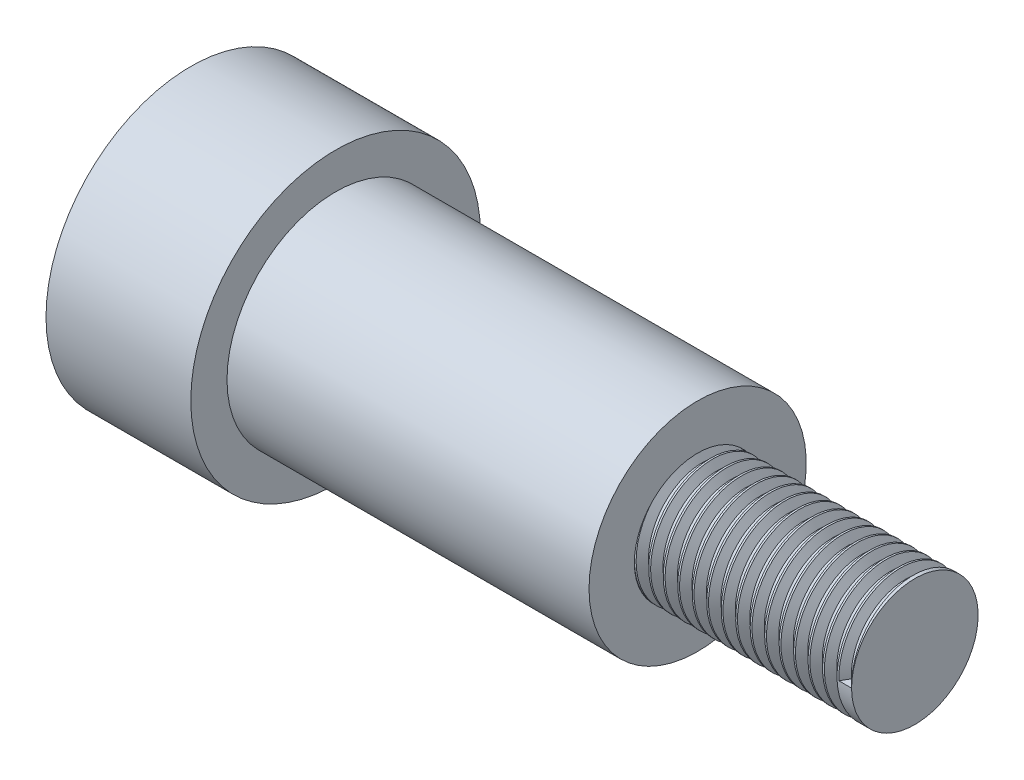
SolidWorks part; units mm, degrees
ref_plane "Front Plane" through (0, 0, 0) normal (0, 0, 1) x (1, 0, 0)
ref_plane "Top Plane" through (0, 0, 0) normal (0, 1, 0) x (1, 0, 0)
ref_plane "Right Plane" through (0, 0, 0) normal (1, 0, 0) x (0, 0, -1)
sketch "Sketch1" plane through (0, 0, 0) normal (0, 0, 1) x (1, 0, 0)
  line L0 (0, 0) -> (63.5, 0)
  line L1 (63.5, 0) -> (63.5, 5.5499)
  line L2 (63.5, 5.5499) -> (44.45, 5.5499)
  line L3 (12.7, 9.525) -> (12.7, 12.7)
  line L4 (12.7, 12.7) -> (0, 12.7)
  line L5 (0, 12.7) -> (0, 0)
  line L6 (12.7, 9.525) -> (44.45, 9.525)
  line L7 (44.45, 9.525) -> (44.45, 5.5499)
  dimension "D1" = 31.75
  dimension "D2" = 5.5499
  dimension "D3" = 12.7
  dimension "D4" = 12.7
  dimension "D5" = 19.05
  dimension "D6" = 9.525
revolve "Revolve1" add sketch "Sketch1" angle 360 about L0
thread "Thread1" pitch 1.27 method cut profile "Thread Profile1" start angle 0, offset 0, length 0, pitch 1.27, diameter 11.0998
ref_plane "Plane1" through (63.5, 0, 5.5499) normal (0, -1, 0) x (0, 0, 1)
sketch "Thread Profile1" plane through (63.5, 0, 5.5499) normal (0, -1, 0) x (0, 0, 1)
  line L0 (0, 0) -> (0, 1.27) construction
  line L11 (0, 0) -> (0, 1.1112)
  line L12 (0, 1.1112) -> (-0.6874, 0.7144)
  line L13 (-0.6874, 0.7144) -> (-0.6874, 0.3969)
  line L15 (-0.6874, 0.3969) -> (0, 0)
  line L17 (-0.6874, 0.5556) -> (0, 0.5556) construction
  point P2 (0, 0)
  dimension "Pitch" = 1.27
  dimension "Profile_Angle" = 60
  dimension "Profile_Land" = 0.3175
  dimension "Profile_Height" = 0.6874
